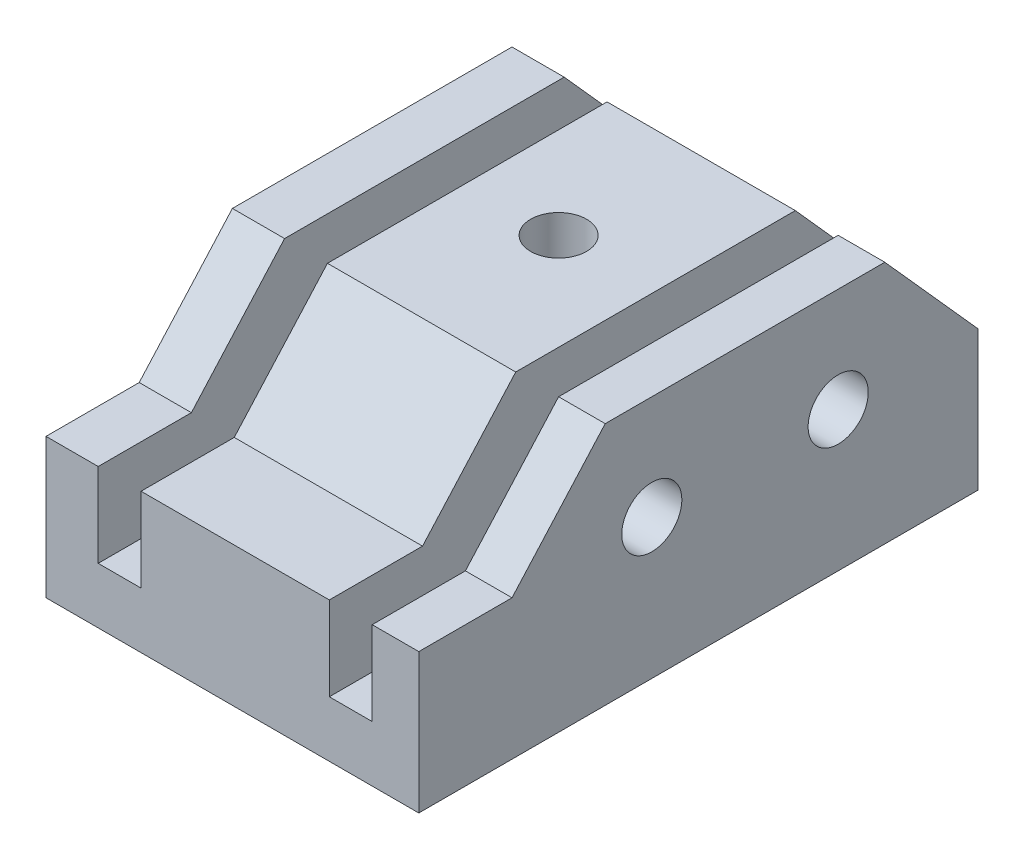
SolidWorks part; units mm, degrees
ref_plane "Front Plane" through (0, 0, 0) normal (0, 0, 1) x (1, 0, 0)
ref_plane "Top Plane" through (0, 0, 0) normal (0, 1, 0) x (1, 0, 0)
ref_plane "Right Plane" through (0, 0, 0) normal (1, 0, 0) x (0, 0, -1)
sketch "Sketch1" plane through (0, 0, 0) normal (1, 0, 0) x (0, 0, -1)
  line L1 (0, 0) -> (63.5, 0)
  line L2 (0, 0) -> (0, 6.35)
  line L3 (0, 6.35) -> (63.5, 6.35)
  line L4 (63.5, 0) -> (63.5, 6.35)
  dimension "D1" = 6.35
  dimension "D2" = 63.5
extrude "Boss-Extrude1" add sketch "Sketch1" against normal blind 50.8
sketch "Sketch2" plane through (0, 0, 0) normal (1, 0, 0) x (0, 0, -1)
  line L0 (0, 6.35) -> (0, 19.05)
  line L1 (0, 19.05) -> (12.7, 33.249)
  line L2 (12.7, 33.249) -> (50.8, 33.249)
  line L3 (50.8, 33.249) -> (63.5, 19.05)
  line L4 (63.5, 19.05) -> (63.5, 6.35)
  line L5 (63.5, 6.35) -> (0, 6.35)
  point P7 (31.75, 33.249)
  point P10 (31.75, 6.35)
  dimension "D1" = 38.1
  dimension "D2" = 12.7
  dimension "D3" = 12.7
  dimension "D4" = 19.05
  dimension "D5" = 19.05
extrude "Boss-Extrude2" add sketch "Sketch2" against normal blind 50.8
sketch "Sketch10" plane through (0, 0, -63.5) normal (0, 0, -1) x (-1, 0, 0)
  line L1 (50.8, 33.249) -> (0, 33.249) construction
  line L3 (6.35, 7.62) -> (6.35, 33.249)
  line L4 (6.35, 33.249) -> (12.192, 33.249)
  line L5 (12.192, 7.62) -> (12.192, 33.249)
  line L6 (6.35, 7.62) -> (12.192, 7.62)
  line L8 (50.8, 0) -> (0, 0) construction
  point P11 (12.192, 7.62)
  dimension "D1" = 7.62
  dimension "D2" = 5.842
  dimension "D3" = 6.35
extrude "Cut-Extrude1" cut sketch "Sketch10" against normal through all
pattern_linear "LPattern3" count 2 spacing 31.496 along (-1, 0, 0) of "Cut-Extrude1"
sketch "Sketch11" plane through (0, 0, 0) normal (1, 0, 0) x (0, 0, -1)
  circle A0 centre (19.05, 19.05) radius 4.0957
  circle A1 centre (19.05, 19.05) radius 7.9375 construction
  circle A2 centre (44.45, 19.05) radius 4.0958
  circle A3 centre (44.45, 19.05) radius 7.9375 construction
  dimension "D1" = 8.1915
  dimension "D3" = 15.875
  dimension "D4" = 8.1915
  dimension "D6" = 15.875
  dimension "D2" = 6.35
  dimension "D5" = 6.35
extrude "Cut-Extrude2" cut sketch "Sketch11" against normal through all
sketch "Sketch14" plane through (0, 33.249, 0) normal (0, 1, 0) x (1, 0, 0)
  line L3 (-37.846, 12.7) -> (-37.846, 50.8) construction
  point P0 (-25.4, 31.75)
  point P4 (-37.846, 31.75)
  dimension "D1" = 12.446
sketch "Sketch17" plane through (0, 40.0201, -44.7438) normal (0, 0.6667, -0.7454) x (-1, 0, 0)
  line L0 (12.192, -28.1343) -> (12.192, -9.0843) construction
  line L1 (37.846, -9.0843) -> (12.192, -9.0843) construction
  point P0 (25.019, -18.6093)
  point P4 (12.192, -18.6093)
  point P7 (25.019, -9.0843)
sketch "Sketch18" plane through (0, 8.4667, 9.466) normal (0, 0.6667, 0.7454) x (1, 0, 0)
  line L0 (-12.192, 33.249) -> (-12.192, 14.199) construction
  line L1 (-37.846, 33.249) -> (-12.192, 33.249) construction
  point P0 (-25.019, 23.724)
  point P1 (-25.019, 23.724)
  point P4 (-12.192, 23.724)
  point P7 (-25.019, 33.249)
ref_plane "Plane2" through (0, 33.02, 0) normal (0, -1, 0) x (-1, 0, 0)
fillet "Fillet1" [suppressed] radius 2.54
sketch "Sketch22" plane through (0, 0, 0) normal (0, 0, 1) x (1, 0, 0)
  line L0 (-50.8, 19.05) -> (-50.8, 0) construction
  line L1 (0, 0) -> (-50.8, 0)
  line L2 (0, 0) -> (0, 7.62)
  line L3 (-6.35, 7.62) -> (-12.192, 7.62)
  line L4 (-50.8, 0) -> (-50.8, 7.62)
  line L5 (-37.846, 7.62) -> (-37.846, 19.05)
  line L6 (-37.846, 19.05) -> (-12.192, 19.05)
  line L7 (-12.192, 19.05) -> (-12.192, 7.62)
  line L8 (-37.846, 7.62) -> (-43.688, 7.62)
  line L9 (-50.8, 7.62) -> (-50.8, 19.05)
  line L10 (-50.8, 19.05) -> (-43.688, 19.05)
  line L11 (-43.688, 19.05) -> (-43.688, 7.62)
  line L12 (-6.35, 7.62) -> (-6.35, 19.05)
  line L13 (-6.35, 19.05) -> (0, 19.05)
  line L14 (0, 19.05) -> (0, 7.62)
extrude "Boss-Extrude3" add sketch "Sketch22" along normal blind 12.7
sketch "Sketch23" plane through (0, 33.249, 0) normal (0, 1, 0) x (1, 0, 0)
  line L0 (-25.4, 63.5) -> (-25.4, -12.7) construction
  line L1 (-50.8, 63.5) -> (0, 63.5) construction
  line L2 (-50.8, -12.7) -> (0, -12.7) construction
  circle A0 centre (-25.4, 31.75) radius 3.81
  point P15 (-34.579, 50.8)
  dimension "D1" = 7.62
extrude "Cut-Extrude6" cut sketch "Sketch23" against normal through all
sketch "Sketch24" plane through (0, 0, 0) normal (0, -1, 0) x (1, 0, 0)
  line L0 (-25.4, -63.5) -> (-25.4, 12.7) construction
  line L1 (-13.97, -50.8) -> (-36.83, -50.8)
  line L2 (-13.97, -50.8) -> (-13.97, 7.62)
  line L3 (-13.97, 7.62) -> (-36.83, 7.62)
  line L4 (-36.83, -50.8) -> (-36.83, 7.62)
  line L5 (-50.8, -63.5) -> (0, -63.5) construction
  line L6 (-50.8, 12.7) -> (0, 12.7) construction
  line L7 (-25.4, -50.8) -> (-25.4, 7.62) construction
  circle A0 centre (-25.4, -31.75) radius 3.81 construction
  dimension "D1" = 58.42
  dimension "D2" = 19.05
  dimension "D3" = 22.86
extrude "Cut-Extrude7" cut sketch "Sketch24" against normal blind 4.58
sketch "Sketch25" plane through (0, 4.58, 0) normal (0, -1, 0) x (1, 0, 0)
  circle A0 centre (-25.4, -31.75) radius 7
  dimension "D1" = 14
extrude "Cut-Extrude8" cut sketch "Sketch25" against normal blind 2.8
sketch "Sketch26" plane through (0, 4.58, 0) normal (0, -1, 0) x (-1, 0, 0)
  line L0 (25.4, 50.8) -> (25.4, -7.62) construction
  line L1 (36.83, 50.8) -> (13.97, 50.8) construction
  line L2 (13.97, -7.62) -> (36.83, -7.62) construction
  circle A0 centre (30.4, 46.15) radius 3
  circle A1 centre (20.4, 46.15) radius 3
  circle A2 centre (25.4, 31.75) radius 7 construction
  circle A3 centre (20.4, -1.897) radius 3
  circle A4 centre (30.4, -1.897) radius 3
  dimension "D2" = 6
  dimension "D5" = 5
  dimension "D1" = 14.4
  dimension "D3" = 10
  dimension "D4" = 10
extrude "Cut-Extrude9" cut sketch "Sketch26" against normal blind 10
